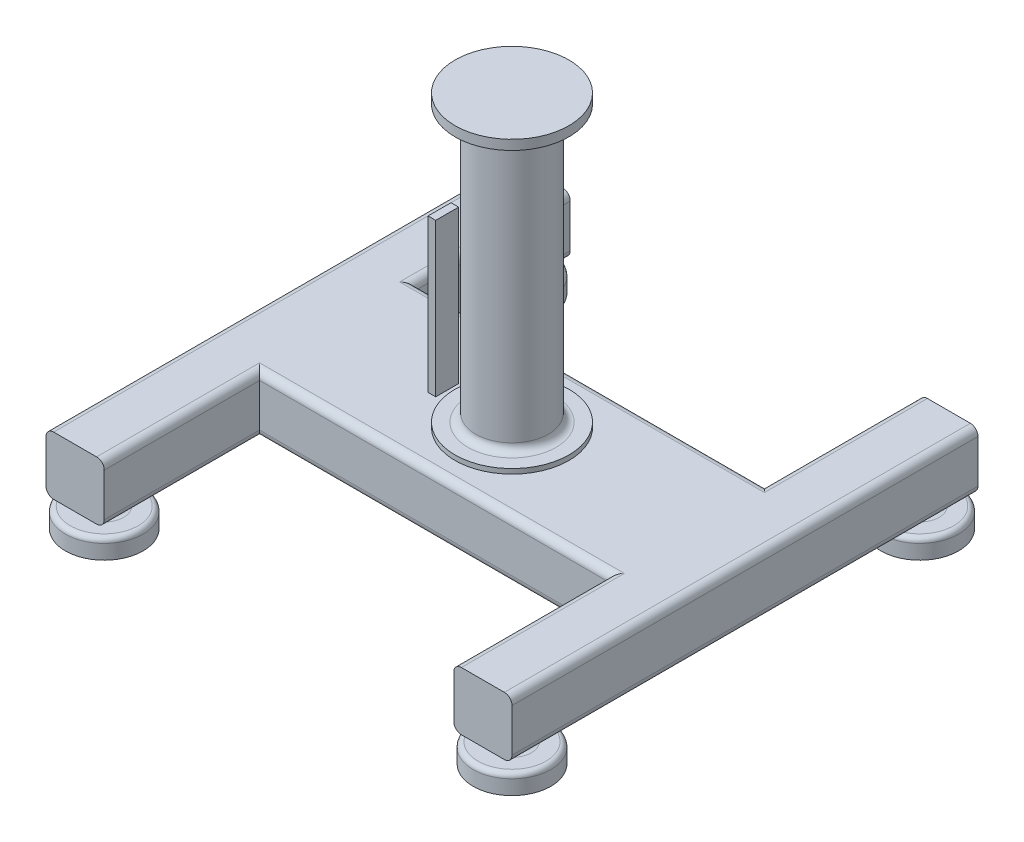
SolidWorks part; units mm, degrees
ref_plane "Front Plane" through (0, 0, 0) normal (0, 0, 1) x (1, 0, 0)
ref_plane "Top Plane" through (0, 0, 0) normal (0, 1, 0) x (1, 0, 0)
ref_plane "Right Plane" through (0, 0, 0) normal (1, 0, 0) x (0, 0, -1)
sketch "Sketch1" plane through (0, 0, 0) normal (0, 1, 0) x (1, 0, 0)
  line L1 (304.8, 304.8) -> (-304.8, 304.8)
  line L2 (304.8, 304.8) -> (304.8, -304.8)
  line L3 (304.8, -304.8) -> (-304.8, -304.8)
  line L4 (-304.8, 304.8) -> (-304.8, -304.8)
  line L5 (304.8, 304.8) -> (-304.8, -304.8) construction
  line L6 (304.8, -304.8) -> (-304.8, 304.8) construction
  point P0 (0, 0)
  dimension "D1" = 609.6
  dimension "D2" = 609.6
extrude "Boss-Extrude1" add sketch "Sketch1" along normal blind 76.2
sketch "Sketch2" plane through (0, 76.2, 0) normal (0, 1, 0) x (1, 0, 0)
  line L0 (-228.6, -304.8) -> (-228.6, -101.6)
  line L1 (-304.8, -304.8) -> (304.8, -304.8) construction
  line L2 (-228.6, -101.6) -> (228.6, -101.6)
  line L3 (228.6, -101.6) -> (228.6, -304.8)
  line L4 (228.6, -304.8) -> (304.8, -304.8) construction
  line L5 (-228.6, -304.8) -> (-304.8, -304.8) construction
  line L6 (-228.6, -304.8) -> (228.6, -304.8)
  line L7 (-304.8, 0) -> (304.8, 0) construction
  line L8 (-304.8, 304.8) -> (-304.8, -304.8) construction
  line L9 (304.8, -304.8) -> (304.8, 304.8) construction
  line L10 (228.6, 101.6) -> (228.6, 304.8)
  line L11 (-228.6, 101.6) -> (228.6, 101.6)
  line L12 (-228.6, 304.8) -> (228.6, 304.8)
  line L13 (-228.6, 304.8) -> (-228.6, 101.6)
  dimension "D1" = 457.2
  dimension "D2" = 203.2
extrude "Cut-Extrude1" cut sketch "Sketch2" against normal through all
fillet "Fillet1" radius 10 16 edges at (0, 76.2, -101.6) (0, 0, -101.6) (228.6, 0, -203.2) (228.6, 76.2, -203.2) (304.8, 0, 0) (304.8, 76.2, 0) (228.6, 76.2, 203.2) (228.6, 0, 203.2) (0, 0, 101.6) (0, 76.2, 101.6) (-228.6, 0, 203.2) (-228.6, 76.2, 203.2) (-304.8, 76.2, 0) (-304.8, 0, 0) (-228.6, 0, -203.2) (-228.6, 76.2, -203.2)
sketch "Sketch4" plane through (0, 0, 0) normal (0, -1, 0) x (1, 0, 0)
  line L0 (-266.7, 304.8) -> (-266.7, 266.7) construction
  line L1 (-294.8, 304.8) -> (-238.6, 304.8) construction
  circle A0 centre (-266.7, 266.7) radius 12.7
  circle A1 centre (266.7, 266.7) radius 12.7
  circle A2 centre (266.7, -266.7) radius 12.7
  circle A3 centre (-266.7, -266.7) radius 12.7
  point P14 (0, 0)
  dimension "D2" = 25.4
  dimension "D1" = 38.1
  dimension "D3" = 4
extrude "Boss-Extrude2" add sketch "Sketch4" along normal blind 12.7
sketch "Sketch5" plane through (0, -12.7, 0) normal (0, -1, 0) x (1, 0, 0)
  circle A0 centre (-266.7, 266.7) radius 50.8
  circle A1 centre (266.7, 266.7) radius 50.8
  circle A2 centre (266.7, -266.7) radius 50.8
  circle A3 centre (-266.7, -266.7) radius 50.8
  point P12 (0, 0)
  dimension "D1" = 101.6
  dimension "D2" = 4
extrude "Boss-Extrude3" add sketch "Sketch5" along normal blind 25.4
fillet "Fillet3" radius 12.7 4 edges at (266.7, -12.7, 254) (266.7, -12.7, -279.4) (-266.7, -12.7, 254) (-266.7, -12.7, -279.4)
fillet "Fillet4" radius 6.35 4 edges at (-266.7, -12.7, -317.5) (266.7, -12.7, -317.5) (266.7, -12.7, 215.9) (-266.7, -12.7, 215.9)
sketch "Sketch6" plane through (0, 76.2, 0) normal (0, 1, 0) x (1, 0, 0)
  circle A0 centre (0, 0) radius 74.5
  dimension "D1" = 149
extrude "Boss-Extrude4" add sketch "Sketch6" along normal blind 6.35
sketch "Sketch7" plane through (0, 82.55, 0) normal (0, 1, 0) x (1, 0, 0)
  circle A0 centre (0, 0) radius 47.5
  dimension "D1" = 95
extrude "Boss-Extrude5" add sketch "Sketch7" along normal blind 360.3
sketch "Sketch8" plane through (0, 442.85, 0) normal (0, 1, 0) x (1, 0, 0)
  circle A0 centre (0, 0) radius 74.5
  dimension "D1" = 149
extrude "Boss-Extrude6" add sketch "Sketch8" along normal blind 12.7
fillet "Fillet5" radius 10 2 edges at (0, 442.85, 47.5) (0, 82.55, 47.5)
sketch "Sketch9" plane through (0, 76.2, 0) normal (0, 1, 0) x (1, 0, 0)
  line L0 (-304.8, 0) -> (-89.8, 0) construction
  line L1 (-304.8, -304.8) -> (-304.8, 304.8) construction
  line L3 (-94.8, -15) -> (-84.8, -15)
  line L4 (-94.8, -15) -> (-94.8, 15)
  line L5 (-94.8, 15) -> (-84.8, 15)
  line L6 (-84.8, -15) -> (-84.8, 15)
  line L7 (-94.8, -15) -> (-84.8, 15) construction
  line L8 (-94.8, 15) -> (-84.8, -15) construction
  dimension "D1" = 210
  dimension "D2" = 10
  dimension "D3" = 30
extrude "Boss-Extrude7" add sketch "Sketch9" along normal blind 200
